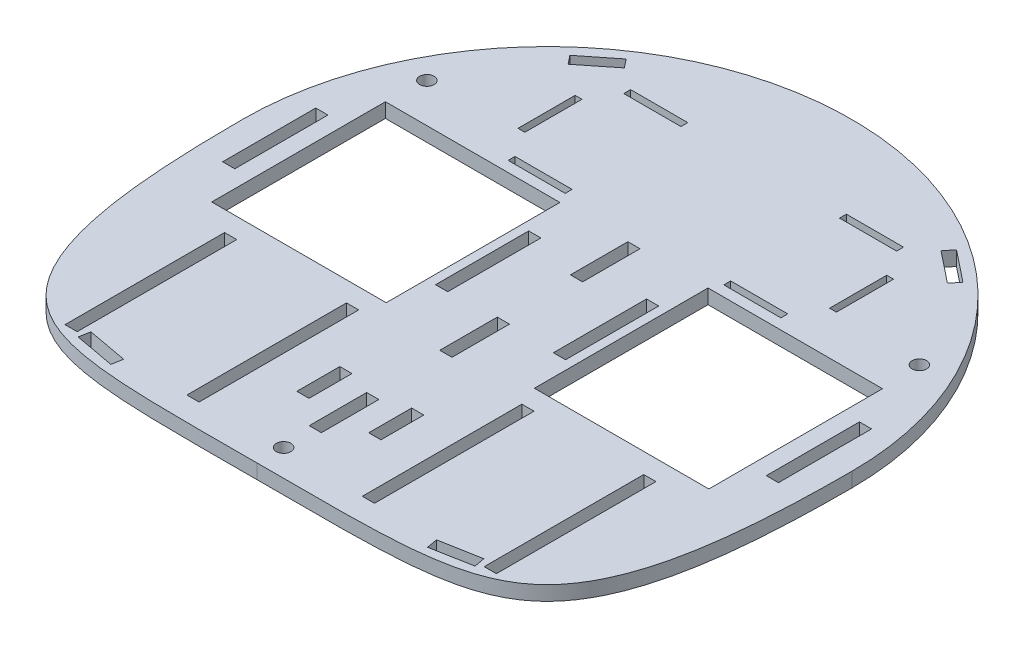
SolidWorks part; units mm, degrees
ref_plane "Front Plane" through (0, 0, 0) normal (0, 0, 1) x (1, 0, 0)
ref_plane "Top Plane" through (0, 0, 0) normal (0, 1, 0) x (1, 0, 0)
ref_plane "Right Plane" through (0, 0, 0) normal (1, 0, 0) x (0, 0, -1)
sketch "Sketch1" plane through (0, 0, 0) normal (0, 1, 0) x (1, 0, 0)
  line L0 (0, 0) -> (-157.9039, -157.9039) construction
  line L1 (0, -127) -> (0, 133.35) construction
  arc A0 (133.35, 0) -> (-133.35, 0) centre (0, 0) ccw
  spline S0 degree 3 poles (-133.35, 0) (-133.35, -51.198) (-123.8034, -129.8051) (-58.428, -127) (0, -127) knots 0 0 0 0 0.502616 1 1 1 1
  spline S1 degree 3 poles (133.35, 0) (133.35, -51.198) (123.8034, -129.8051) (58.428, -127) (0, -127) knots 0 0 0 0 0.502616 1 1 1 1
  dimension "D1" = 266.7
extrude "Base" add sketch "Sketch1" along normal blind 6.35
sketch "ShaftLayout" plane through (0, 6.35, 0) normal (0, 1, 0) x (1, 0, 0)
  line L0 (-133.35, 0) -> (133.35, 0) construction
  line L1 (0, 133.35) -> (0, -127) construction
  line L2 (-114.7053, -6.35) -> (-104.7993, -6.35)
  line L3 (-36.3853, -38) -> (-94.3853, -38)
  line L4 (-36.3853, -38) -> (-36.3853, 38)
  line L5 (-36.3853, 38) -> (-94.3853, 38)
  line L6 (-94.3853, -38) -> (-94.3853, 38)
  line L7 (-36.3853, -38) -> (-94.3853, 38) construction
  line L8 (-36.3853, 38) -> (-94.3853, -38) construction
  line L9 (-102.0053, -15.875) -> (-104.7993, -15.875)
  line L10 (-102.0053, -15.875) -> (-102.0053, 15.875)
  line L11 (-102.0053, 15.875) -> (-104.7993, 15.875)
  line L12 (-104.7993, -15.875) -> (-104.7993, 15.875)
  line L13 (-102.0053, -15.875) -> (-104.7993, 15.875) construction
  line L14 (-102.0053, 15.875) -> (-104.7993, -15.875) construction
  line L15 (-114.7053, -6.35) -> (-114.7053, 6.35)
  line L16 (-104.7993, -6.35) -> (-104.7993, 6.35)
  line L17 (-114.7053, 6.35) -> (-104.7993, 6.35)
  line L18 (-114.7053, -6.35) -> (-104.7993, 6.35) construction
  line L19 (-104.7993, -6.35) -> (-114.7053, 6.35) construction
  line L20 (-116.2928, -9.525) -> (-114.7053, -9.525)
  line L21 (-116.2928, -9.525) -> (-116.2928, 9.525)
  line L22 (-114.7053, -9.525) -> (-114.7053, 9.525)
  line L23 (-116.2928, 9.525) -> (-114.7053, 9.525)
  line L24 (-116.2928, -9.525) -> (-114.7053, 9.525) construction
  line L25 (-114.7053, -9.525) -> (-116.2928, 9.525) construction
  line L26 (-127.4053, -7.9375) -> (-116.2928, -7.9375)
  line L27 (-127.4053, -7.9375) -> (-127.4053, 7.9375)
  line L28 (-116.2928, -7.9375) -> (-116.2928, 7.9375)
  line L29 (-127.4053, 7.9375) -> (-116.2928, 7.9375)
  line L30 (-127.4053, -7.9375) -> (-116.2928, 7.9375) construction
  line L31 (-116.2928, -7.9375) -> (-127.4053, 7.9375) construction
  line L32 (-17.3353, -7.9375) -> (-28.4478, -7.9375)
  line L33 (-30.0353, -9.525) -> (-28.4478, -9.525)
  line L34 (-30.0353, -9.525) -> (-30.0353, 9.525)
  line L35 (-30.0353, 9.525) -> (-28.4478, 9.525)
  line L36 (-28.4478, -9.525) -> (-28.4478, 9.525)
  line L37 (-30.0353, -9.525) -> (-28.4478, 9.525) construction
  line L38 (-30.0353, 9.525) -> (-28.4478, -9.525) construction
  line L39 (-17.3353, -7.9375) -> (-17.3353, 7.9375)
  line L40 (-28.4478, -7.9375) -> (-28.4478, 7.9375)
  line L41 (-17.3353, 7.9375) -> (-28.4478, 7.9375)
  line L42 (-17.3353, -7.9375) -> (-28.4478, 7.9375) construction
  line L43 (-28.4478, -7.9375) -> (-17.3353, 7.9375) construction
  line L45 (-67.3853, -10.033) -> (-56.3853, -10.033)
  line L46 (-67.3853, -10.033) -> (-67.3853, 10.033)
  line L47 (-67.3853, 10.033) -> (-56.3853, 10.033)
  line L48 (-56.3853, -10.033) -> (-56.3853, 10.033)
  line L49 (-67.3853, -10.033) -> (-56.3853, 10.033) construction
  line L50 (-67.3853, 10.033) -> (-56.3853, -10.033) construction
  arc A0 (133.35, 0) -> (-133.35, 0) centre (0, 0) ccw construction
  point P10 (-65.3853, 0)
  point P15 (-103.4023, 0)
  point P20 (-29.2416, 0)
  point P21 (-109.7523, 0)
  point P22 (-115.4991, 0)
  point P23 (-121.8491, 0)
  point P40 (-61.8853, 0)
  point P41 (-22.8916, 0)
  dimension "D1" = 58
  dimension "D2" = 76
  dimension "D3" = 7.62
  dimension "D4" = 2.794
  dimension "D5" = 31.75
  dimension "D6" = 9.906
  dimension "D7" = 12.7
  dimension "D8" = 19.05
  dimension "D9" = 1.5875
  dimension "D10" = 12.7
  dimension "D11" = 15.875
  dimension "D12" = 19.05
  dimension "D13" = 1.5875
  dimension "D14" = 15.875
  dimension "D15" = 12.7
  dimension "D16" = 6.35
  dimension "D17" = 20.066
  dimension "D18" = 20
  dimension "D19" = 11
sketch "MotorLayout" plane through (0, 6.35, 0) normal (0, 1, 0) x (1, 0, 0)
  line L0 (-94.3853, -81.74) -> (-114.3853, -81.74) construction
  line L1 (-94.3853, -110.24) -> (-18.3853, -110.24)
  line L2 (-94.3853, -110.24) -> (-94.3853, -53.24)
  line L3 (-94.3853, -53.24) -> (-18.3853, -53.24)
  line L4 (-18.3853, -110.24) -> (-18.3853, -53.24)
  line L5 (-94.3853, -110.24) -> (-18.3853, -53.24) construction
  line L6 (-94.3853, -53.24) -> (-18.3853, -110.24) construction
  line L7 (-114.7053, -92.0587) -> (-104.7993, -92.0587)
  line L8 (-104.7993, -97.615) -> (-102.0053, -97.615)
  line L9 (-104.7993, -97.615) -> (-104.7993, -65.865)
  line L10 (-104.7993, -65.865) -> (-102.0053, -65.865)
  line L11 (-102.0053, -97.615) -> (-102.0053, -65.865)
  line L12 (-104.7993, -97.615) -> (-102.0053, -65.865) construction
  line L13 (-104.7993, -65.865) -> (-102.0053, -97.615) construction
  line L14 (-36.3853, -38) -> (-94.3853, -38) construction
  line L15 (-114.7053, -92.0587) -> (-114.7053, -71.4212)
  line L16 (-104.7993, -92.0587) -> (-104.7993, -71.4212)
  line L17 (-114.7053, -71.4212) -> (-104.7993, -71.4212)
  line L18 (-114.7053, -92.0587) -> (-104.7993, -71.4212) construction
  line L19 (-104.7993, -92.0587) -> (-114.7053, -71.4212) construction
  line L20 (-103.4023, -1000) -> (-103.4023, 49000) construction
  line L21 (-34.8953, -53.24) -> (-34.8953, -110.24) construction
  point P0 (-56.3853, -81.74)
  point P7 (-103.4023, -81.74)
  point P14 (-109.7523, -81.74)
  dimension "D1" = 20
  dimension "D2" = 76
  dimension "D3" = 57
  dimension "D4" = 2.794
  dimension "D5" = 15.24
  dimension "D6" = 31.75
  dimension "D7" = 20.6375
  dimension "D8" = 12.7
  dimension "D9" = 7.62
  dimension "D10" = 16.51
sketch "Sketch6" plane through (0, 6.35, 0) normal (0, 1, 0) x (1, 0, 0)
  line L0 (-36.3853, -38) -> (-36.3853, 38) construction
  line L1 (-32.4166, -38) -> (-108.7681, -38)
  line L2 (-32.4166, -38) -> (-32.4166, 38)
  line L3 (-32.4166, 38) -> (-108.7681, 38)
  line L4 (-108.7681, -38) -> (-108.7681, 38)
  line L5 (-28.4478, -9.525) -> (-28.4478, 9.525) construction
  line L6 (-104.7993, -15.875) -> (-104.7993, 15.875) construction
  line L7 (0, 133.35) -> (0, -127) construction
  line L8 (28.4478, 20.3835) -> (23.1138, -20.3835) construction
  line L9 (28.4478, -20.3835) -> (23.1138, 20.3835) construction
  line L10 (116.2928, 20.3835) -> (121.6268, -20.3835) construction
  line L11 (116.2928, -20.3835) -> (121.6268, 20.3835) construction
  line L12 (-133.35, 0) -> (133.35, 0) construction
  line L13 (-116.2928, -20.3835) -> (-121.6268, -20.3835)
  line L14 (-116.2928, -20.3835) -> (-116.2928, 20.3835)
  line L15 (-116.2928, 20.3835) -> (-121.6268, 20.3835)
  line L16 (-121.6268, -20.3835) -> (-121.6268, 20.3835)
  line L17 (-116.2928, -20.3835) -> (-121.6268, 20.3835) construction
  line L18 (-116.2928, 20.3835) -> (-121.6268, -20.3835) construction
  line L19 (-116.2928, -9.525) -> (-116.2928, 9.525) construction
  line L20 (-127.4053, 7.9375) -> (-116.2928, 7.9375) construction
  line L21 (-17.3353, 7.9375) -> (-28.4478, 7.9375) construction
  line L22 (-28.4478, -20.3835) -> (-23.1138, -20.3835)
  line L23 (-28.4478, -20.3835) -> (-28.4478, 20.3835)
  line L24 (-28.4478, 20.3835) -> (-23.1138, 20.3835)
  line L25 (-23.1138, -20.3835) -> (-23.1138, 20.3835)
  line L26 (-28.4478, -20.3835) -> (-23.1138, 20.3835) construction
  line L27 (-28.4478, 20.3835) -> (-23.1138, -20.3835) construction
  line L28 (23.1138, -20.3835) -> (23.1138, 20.3835)
  line L29 (28.4478, 20.3835) -> (23.1138, 20.3835)
  line L30 (28.4478, -20.3835) -> (28.4478, 20.3835)
  line L31 (28.4478, -20.3835) -> (23.1138, -20.3835)
  line L32 (121.6268, -20.3835) -> (121.6268, 20.3835)
  line L33 (116.2928, 20.3835) -> (121.6268, 20.3835)
  line L34 (116.2928, -20.3835) -> (116.2928, 20.3835)
  line L35 (116.2928, -20.3835) -> (121.6268, -20.3835)
  line L36 (108.7681, -38) -> (108.7681, 38)
  line L37 (32.4166, 38) -> (108.7681, 38)
  line L38 (32.4166, -38) -> (32.4166, 38)
  line L39 (32.4166, -38) -> (108.7681, -38)
  point P16 (-118.9598, 0)
  point P27 (-25.7808, 0)
  point P44 (25.7808, 0)
  point P45 (118.9598, 0)
  dimension "D1" = 3.9688
  dimension "D2" = 3.9688
  dimension "D3" = 12.446
  dimension "D4" = 12.446
  dimension "D5" = 5.334
  dimension "D6" = 5.334
extrude "WheelShaftCut" cut sketch "Sketch6" against normal through all
sketch "Sketch8" plane through (0, 6.35, 0) normal (0, 1, 0) x (1, 0, 0)
  line L0 (-94.3853, -81.74) -> (-18.3853, -81.74) construction
  line L1 (-18.3853, -110.24) -> (-18.3853, -53.24) construction
  line L2 (-94.3853, -53.24) -> (-18.3853, -53.24) construction
  line L3 (-35.7113, -116.59) -> (-41.0453, -116.59)
  line L4 (-35.7113, -116.59) -> (-35.7113, -46.763)
  line L5 (-35.7113, -46.763) -> (-41.0453, -46.763)
  line L6 (-41.0453, -116.59) -> (-41.0453, -46.763)
  line L7 (-35.7113, -116.59) -> (-41.0453, -46.763) construction
  line L8 (-35.7113, -46.763) -> (-41.0453, -116.59) construction
  line L9 (18.3853, -72.342) -> (13.0513, -91.138) construction
  line L10 (18.3853, -91.138) -> (13.0513, -72.342) construction
  line L11 (18.3853, -81.74) -> (15.7183, -81.74) construction
  line L12 (89.0513, -46.763) -> (94.3853, -116.59) construction
  line L13 (89.0513, -116.59) -> (94.3853, -46.763) construction
  line L14 (35.7113, -46.763) -> (41.0453, -116.59) construction
  line L15 (-89.0513, -116.59) -> (-94.3853, -116.59)
  line L16 (-89.0513, -116.59) -> (-89.0513, -46.763)
  line L17 (-89.0513, -46.763) -> (-94.3853, -46.763)
  line L18 (-94.3853, -116.59) -> (-94.3853, -46.763)
  line L19 (-89.0513, -116.59) -> (-94.3853, -46.763) construction
  line L20 (-89.0513, -46.763) -> (-94.3853, -116.59) construction
  line L21 (-94.3853, -110.24) -> (-94.3853, -53.24) construction
  line L22 (0, 133.35) -> (0, -127) construction
  line L23 (35.7113, -116.59) -> (41.0453, -46.763) construction
  line L24 (94.3853, -81.74) -> (18.3853, -81.74) construction
  line L25 (13.0513, -91.138) -> (13.0513, -72.342)
  line L26 (18.3853, -72.342) -> (13.0513, -72.342)
  line L27 (18.3853, -91.138) -> (18.3853, -72.342)
  line L28 (18.3853, -91.138) -> (13.0513, -91.138)
  line L29 (94.3853, -116.59) -> (94.3853, -46.763)
  line L30 (89.0513, -46.763) -> (94.3853, -46.763)
  line L31 (89.0513, -116.59) -> (89.0513, -46.763)
  line L32 (89.0513, -116.59) -> (94.3853, -116.59)
  line L33 (41.0453, -116.59) -> (41.0453, -46.763)
  line L34 (35.7113, -46.763) -> (41.0453, -46.763)
  line L35 (35.7113, -116.59) -> (35.7113, -46.763)
  line L36 (35.7113, -116.59) -> (41.0453, -116.59)
  line L42 (-18.3853, -81.74) -> (-15.7183, -81.74) construction
  line L44 (-18.3853, -91.138) -> (-13.0513, -91.138)
  line L45 (-18.3853, -91.138) -> (-18.3853, -72.342)
  line L46 (-18.3853, -72.342) -> (-13.0513, -72.342)
  line L47 (-13.0513, -91.138) -> (-13.0513, -72.342)
  line L48 (-18.3853, -91.138) -> (-13.0513, -72.342) construction
  line L49 (-18.3853, -72.342) -> (-13.0513, -91.138) construction
  point P6 (-63.7079, -81.74)
  point P7 (-38.2513, -81.74)
  point P19 (-91.5913, -81.74)
  point P39 (91.5913, -81.74)
  point P40 (38.2513, -81.74)
  dimension "D1" = 5.334
  dimension "D2" = 6.477
  dimension "D4" = 5.334
  dimension "D5" = 18.796
  dimension "D3" = 2
extrude "MotorCut" cut sketch "Sketch8" against normal through all
sketch "BatteryLayout" plane through (0, 6.35, 0) normal (0, 1, 0) x (1, 0, 0)
  line L0 (0, 133.35) -> (0, -127) construction
  line L1 (-32.4166, 38) -> (-108.7681, 38) construction
  line L2 (-66.675, 45.62) -> (66.675, 45.62)
  line L3 (-66.675, 45.62) -> (-66.675, 93.245)
  line L4 (-66.675, 93.245) -> (66.675, 93.245)
  line L5 (66.675, 45.62) -> (66.675, 93.245)
  line L6 (-66.675, 45.62) -> (66.675, 93.245) construction
  line L7 (-66.675, 93.245) -> (66.675, 45.62) construction
  arc A0 (133.35, 0) -> (-133.35, 0) centre (0, 0) ccw construction
  point P6 (0, 69.4325)
  dimension "D1" = 133.35
  dimension "D2" = 47.625
  dimension "D3" = 7.62
sketch "Sketch10" plane through (0, 6.35, 0) normal (0, 1, 0) x (1, 0, 0)
  line L0 (-66.675, 93.245) -> (66.675, 93.245) construction
  line L1 (-59.69, 42.62) -> (-34.69, 42.62)
  line L2 (-59.69, 42.62) -> (-59.69, 45.62)
  line L3 (-59.69, 45.62) -> (-34.69, 45.62)
  line L4 (-34.69, 42.62) -> (-34.69, 45.62)
  line L5 (-59.69, 42.62) -> (-34.69, 45.62) construction
  line L6 (-59.69, 45.62) -> (-34.69, 42.62) construction
  line L7 (-59.69, 96.245) -> (-34.69, 96.245)
  line L8 (-59.69, 96.245) -> (-59.69, 93.245)
  line L9 (-59.69, 93.245) -> (-34.69, 93.245)
  line L10 (-34.69, 96.245) -> (-34.69, 93.245)
  line L11 (-59.69, 96.245) -> (-34.69, 93.245) construction
  line L12 (-59.69, 93.245) -> (-34.69, 96.245) construction
  line L13 (-66.675, 45.62) -> (66.675, 45.62) construction
  line L14 (-66.675, 45.62) -> (-66.675, 93.245) construction
  line L15 (0, 69.4325) -> (-66.675, 69.4325) construction
  line L16 (-66.675, 56.9325) -> (-69.675, 56.9325)
  line L17 (-66.675, 56.9325) -> (-66.675, 81.9325)
  line L18 (-66.675, 81.9325) -> (-69.675, 81.9325)
  line L19 (-69.675, 56.9325) -> (-69.675, 81.9325)
  line L20 (0, 133.35) -> (0, -127) construction
  line L21 (59.69, 93.245) -> (34.69, 96.245) construction
  line L22 (59.69, 96.245) -> (34.69, 93.245) construction
  line L23 (59.69, 45.62) -> (34.69, 42.62) construction
  line L24 (59.69, 42.62) -> (34.69, 45.62) construction
  line L25 (69.675, 56.9325) -> (69.675, 81.9325)
  line L26 (66.675, 81.9325) -> (69.675, 81.9325)
  line L27 (66.675, 56.9325) -> (66.675, 81.9325)
  line L28 (66.675, 56.9325) -> (69.675, 56.9325)
  line L29 (34.69, 96.245) -> (34.69, 93.245)
  line L30 (59.69, 93.245) -> (34.69, 93.245)
  line L31 (59.69, 96.245) -> (59.69, 93.245)
  line L32 (59.69, 96.245) -> (34.69, 96.245)
  line L33 (34.69, 42.62) -> (34.69, 45.62)
  line L34 (59.69, 45.62) -> (34.69, 45.62)
  line L35 (59.69, 42.62) -> (59.69, 45.62)
  line L36 (59.69, 42.62) -> (34.69, 42.62)
  point P0 (-47.19, 44.12)
  point P5 (-47.19, 94.745)
  point P20 (-66.675, 69.4325)
  point P40 (66.675, 69.4325)
  point P41 (47.19, 94.745)
  point P42 (47.19, 44.12)
  dimension "D1" = 3
  dimension "D2" = 3
  dimension "D3" = 25
  dimension "D4" = 25
  dimension "D5" = 6.985
  dimension "D6" = 6.985
  dimension "D7" = 3
  dimension "D8" = 25
extrude "VelcroCut" cut sketch "Sketch10" against normal through all
sketch "Sketch11" plane through (0, 6.35, 0) normal (0, 1, 0) x (1, 0, 0)
  line L0 (0, 133.35) -> (0, -127) construction
  line L1 (-133.35, 0) -> (133.35, 0) construction
  line L3 (-34.69, 45.62) -> (-59.69, 45.62) construction
  line L4 (-69.675, 81.9325) -> (-69.675, 56.9325) construction
  arc A0 (133.35, 0) -> (-133.35, 0) centre (0, 0) ccw construction
  circle A1 centre (0, -115.316) radius 3.175
  circle A2 centre (-107.775, 55.145) radius 3.175
  circle A3 centre (107.775, 55.145) radius 3.175
  dimension "D1" = 6.35
  dimension "D2" = 11.684
  dimension "D3" = 6.35
  dimension "D4" = 9.525
  dimension "D5" = 38.1
extrude "ScrewCut" cut sketch "Sketch11" against normal through all
sketch "Sketch13" plane through (0, 6.35, 0) normal (0, 1, 0) x (1, 0, 0)
  line L0 (0, 133.35) -> (0, -127) construction
  line L1 (-2.667, 12.854) -> (2.667, 12.854)
  line L2 (-2.667, 12.854) -> (-2.667, 38)
  line L3 (-2.667, 38) -> (2.667, 38)
  line L4 (2.667, 12.854) -> (2.667, 38)
  line L5 (-2.667, 12.854) -> (2.667, 38) construction
  line L6 (-2.667, 38) -> (2.667, 12.854) construction
  line L7 (108.7681, 38) -> (32.4166, 38) construction
  line L8 (-2.667, -44.296) -> (2.667, -44.296)
  line L9 (-2.667, -44.296) -> (-2.667, -19.15)
  line L10 (-2.667, -19.15) -> (2.667, -19.15)
  line L11 (2.667, -44.296) -> (2.667, -19.15)
  line L12 (-2.667, -44.296) -> (2.667, -19.15) construction
  line L13 (-2.667, -19.15) -> (2.667, -44.296) construction
  line L14 (-2.667, -101.446) -> (2.667, -101.446)
  line L15 (-2.667, -101.446) -> (-2.667, -76.3)
  line L16 (-2.667, -76.3) -> (2.667, -76.3)
  line L17 (2.667, -101.446) -> (2.667, -76.3)
  line L18 (-2.667, -101.446) -> (2.667, -76.3) construction
  line L19 (-2.667, -76.3) -> (2.667, -101.446) construction
  point P0 (0, 25.427)
  point P10 (0, -31.723)
  point P15 (0, -88.873)
  dimension "D1" = 5.334
  dimension "D2" = 25.146
  dimension "D3" = 0
  dimension "D4" = 3
extrude "SupportStrutCut" cut sketch "Sketch13" against normal through all
sketch "Sketch15" plane through (0, 6.35, 0) normal (0, 1, 0) x (1, 0, 0)
  line L0 (-77.6496, -1116.59) -> (-77.6496, 48883.41) construction
  line L2 (-86.8487, -118.3963) -> (-69.3227, -121.6168)
  line L3 (-86.8487, -118.3963) -> (-85.9765, -113.6498)
  line L4 (-69.3227, -121.6168) -> (-68.4505, -116.8703)
  line L5 (-85.9765, -113.6498) -> (-68.4505, -116.8703)
  line L6 (-86.8487, -118.3963) -> (-68.4505, -116.8703) construction
  line L7 (-69.3227, -121.6168) -> (-85.9765, -113.6498) construction
  line L8 (-83.0115, 92.1755) -> (-69.2866, 103.0746)
  line L9 (-83.0115, 92.1755) -> (-86.0126, 95.9548)
  line L10 (-69.2866, 103.0746) -> (-72.2878, 106.8539)
  line L11 (-86.0126, 95.9548) -> (-72.2878, 106.8539)
  line L12 (-83.0115, 92.1755) -> (-72.2878, 106.8539) construction
  line L13 (-69.2866, 103.0746) -> (-86.0126, 95.9548) construction
  line L14 (0, -1000) -> (0, 49000) construction
  line L15 (69.2866, 103.0746) -> (86.0126, 95.9548) construction
  line L16 (83.0115, 92.1755) -> (72.2878, 106.8539) construction
  line L17 (69.3227, -121.6168) -> (85.9765, -113.6498) construction
  line L18 (86.8487, -118.3963) -> (68.4505, -116.8703) construction
  line L19 (88.7973, -116.59) -> (66.5019, -116.59) construction
  line L20 (86.0126, 95.9548) -> (72.2878, 106.8539)
  line L21 (69.2866, 103.0746) -> (72.2878, 106.8539)
  line L22 (83.0115, 92.1755) -> (86.0126, 95.9548)
  line L23 (83.0115, 92.1755) -> (69.2866, 103.0746)
  line L24 (85.9765, -113.6498) -> (68.4505, -116.8703)
  line L25 (69.3227, -121.6168) -> (68.4505, -116.8703)
  line L26 (86.8487, -118.3963) -> (85.9765, -113.6498)
  line L27 (86.8487, -118.3963) -> (69.3227, -121.6168)
  point P4 (-77.6496, 99.5147)
  point P7 (-77.6496, -117.6333)
  point P30 (77.6496, -117.6333)
  point P31 (77.6496, 99.5147)
  dimension "D1" = 4.826
  dimension "D2" = 17.526
  dimension "D3" = 17.526
  dimension "D4" = 4.826
extrude "TapeSensorCut" cut sketch "Sketch15" against normal through all
